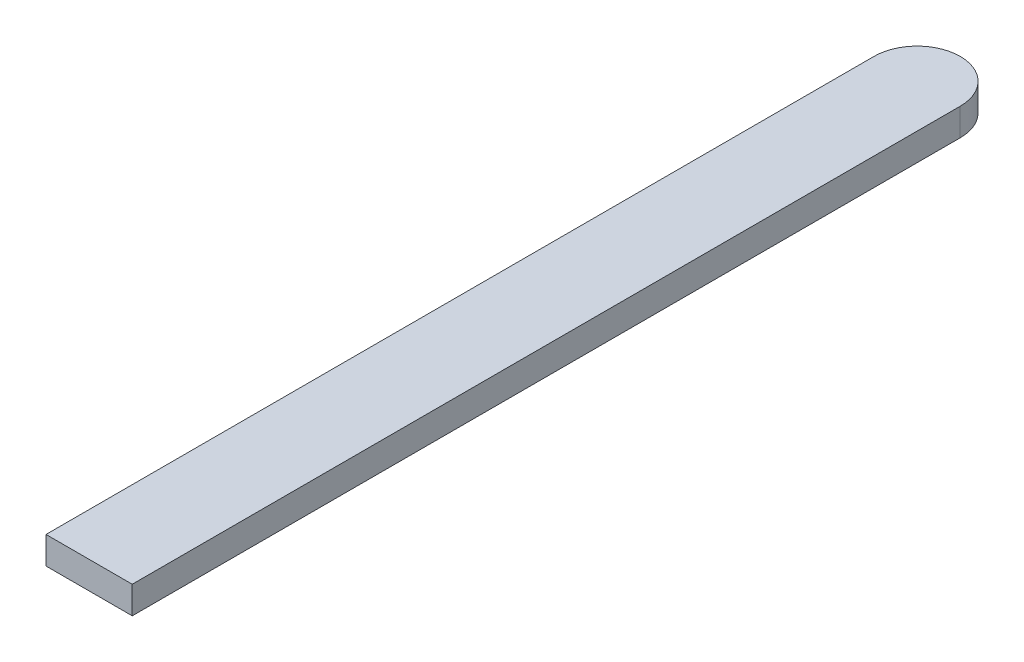
SolidWorks part; units mm, degrees
ref_plane "Front Plane" through (0, 0, 0) normal (0, 0, 1) x (1, 0, 0)
ref_plane "Top Plane" through (0, 0, 0) normal (0, 1, 0) x (1, 0, 0)
ref_plane "Right Plane" through (0, 0, 0) normal (1, 0, 0) x (0, 0, -1)
sketch "Sketch1" plane through (0, 0, 0) normal (0, 1, 0) x (1, 0, 0)
  line L0 (0, 96) -> (0, -96) construction
  line L1 (-10, 96) -> (-10, -96)
  line L7 (10, 96) -> (10, -96)
  line L8 (-10, 96) -> (10, 96) construction
  line L9 (-10, -96) -> (10, -96)
  arc A1 (-10, 96) -> (10, 96) centre (0, 96) cw
  point P3 (0, 0)
  dimension "D1" = 192
  dimension "D2" = 10
  dimension "D3" = 10
extrude "Boss-Extrude1" add sketch "Sketch1" along normal blind 6.35
